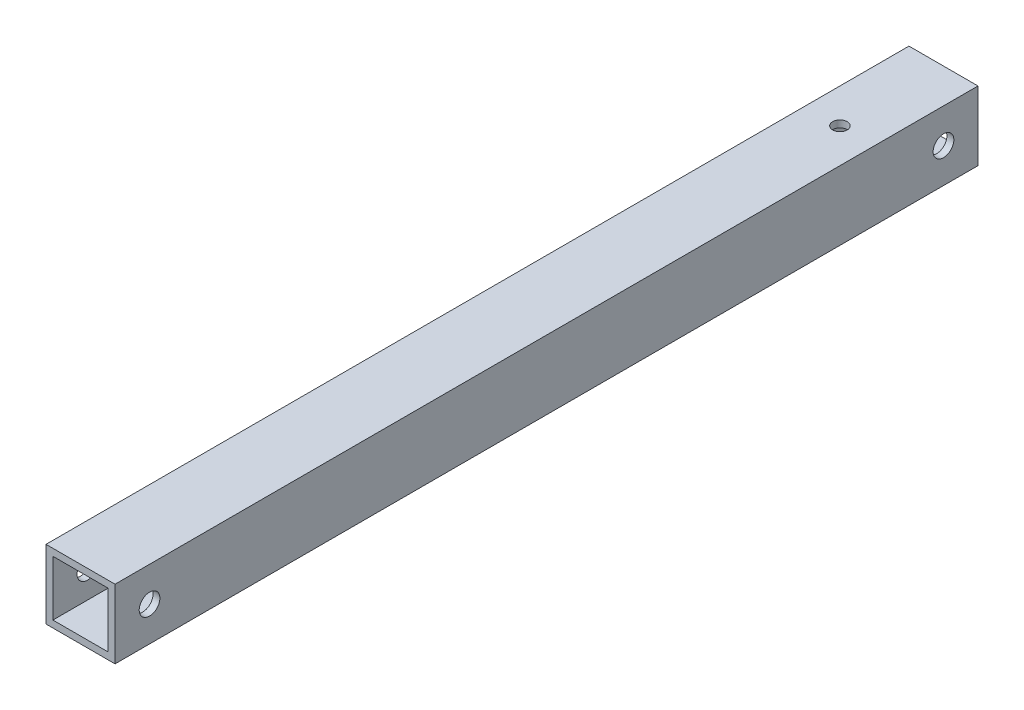
SolidWorks part; units mm, degrees
material "Stop 1060"
ref_plane "Płaszczyzna przednia" through (0, 0, 0) normal (0, 0, 1) x (1, 0, 0)
ref_plane "Płaszczyzna górna" through (0, 0, 0) normal (0, 1, 0) x (1, 0, 0)
ref_plane "Płaszczyzna prawa" through (0, 0, 0) normal (1, 0, 0) x (0, 0, -1)
sketch "Szkic1" plane through (0, 0, 0) normal (0, 0, 1) x (1, 0, 0)
  line L0 (-8, 8) -> (8, 8)
  line L1 (-10, -10) -> (10, -10)
  line L2 (-10, -10) -> (-10, 10)
  line L3 (-10, 10) -> (10, 10)
  line L4 (10, -10) -> (10, 10)
  line L5 (-10, -10) -> (10, 10) construction
  line L6 (-10, 10) -> (10, -10) construction
  line L7 (8, -8) -> (8, 8)
  line L8 (-8, -8) -> (8, -8)
  line L9 (-8, -8) -> (-8, 8)
  point P0 (0, 0)
  dimension "D1" = 20
  dimension "D2" = 20
  dimension "D3" = 2
extrude "Dodanie-wyciągnięcie1" add sketch "Szkic1" along normal blind 250
sketch "Szkic2" plane through (10, 0, 0) normal (1, 0, 0) x (0, 0, -1)
  line L0 (0, -10) -> (0, 10) construction
  line L3 (-250, -10) -> (-250, 10) construction
  circle A0 centre (-10, 0) radius 3
  circle A1 centre (-240, 0) radius 3
  dimension "D1" = 6
  dimension "D3" = 6
  dimension "D2" = 10
  dimension "D4" = 10
extrude "Wytnij-wyciągnięcie1" cut sketch "Szkic2" against normal through all
sketch "Szkic3" plane through (0, 10, 0) normal (0, 1, 0) x (1, 0, 0)
  line L0 (10, -250) -> (10, 0) construction
  line L2 (10, 0) -> (-10, 0) construction
  circle A0 centre (0, -30) radius 2.1
  dimension "D1" = 4.2
  dimension "D2" = 10
  dimension "D3" = 30
extrude "Wytnij-wyciągnięcie2" cut sketch "Szkic3" against normal through all
